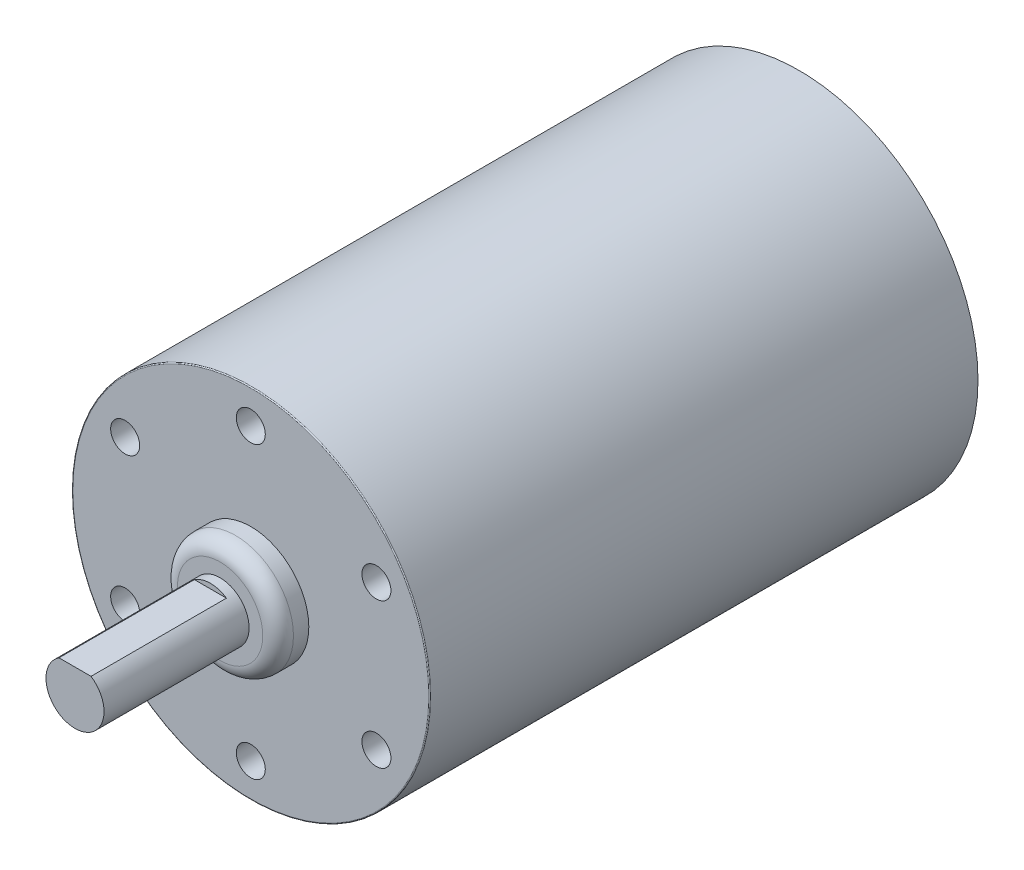
SolidWorks part; units mm, degrees
ref_plane "Front Plane" through (0, 0, 0) normal (0, 0, 1) x (1, 0, 0)
ref_plane "Top Plane" through (0, 0, 0) normal (0, 1, 0) x (1, 0, 0)
ref_plane "Right Plane" through (0, 0, 0) normal (1, 0, 0) x (0, 0, -1)
sketch "Sketch1" plane through (0, 0, 0) normal (0, 0, 1) x (1, 0, 0)
  circle A0 centre (0, 0) radius 18.5
  dimension "D1" = 37
extrude "Boss-Extrude1" add sketch "Sketch1" along normal blind 56.6928
fillet "Fillet3" radius 0.1 1 edges at (18.5, 0, 56.6928)
sketch "Sketch2" plane through (0, 0, 56.6928) normal (0, 0, 1) x (1, 0, 0)
  circle A0 centre (0, 0) radius 6
  dimension "D1" = 12
extrude "Boss-Extrude2" add sketch "Sketch2" along normal blind 3.175
fillet "Fillet2" radius 1.5875 1 edges at (6, 0, 59.8678)
sketch "Sketch5" plane through (0, 0, 59.8678) normal (0, 0, 1) x (1, 0, 0)
  circle A0 centre (0, 0) radius 3
  dimension "D1" = 6
extrude "Boss-Extrude3" add sketch "Sketch5" along normal blind 15
sketch "Sketch6" plane through (0, 0, 74.8678) normal (0, 0, 1) x (1, 0, 0)
  line L0 (-1.6583, 2.5) -> (1.6583, 2.5)
  circle A0 centre (0, 0) radius 3 construction
  circle A1 centre (0, 0) radius 3 construction
  arc A2 (-1.6583, 2.5) -> (1.6583, 2.5) centre (0, 0) cw
  point P7 (0, -3)
  point P8 (0, 0)
  point P9 (0, 0)
  point P10 (1.6583, 2.5)
  point P11 (0, 0)
  dimension "D1" = 5.5
extrude "Cut-Extrude1" cut sketch "Sketch6" against normal blind 14
sketch "Sketch7" plane through (0, 0, 56.6928) normal (0, 0, 1) x (1, 0, 0)
  circle A0 centre (0, 0) radius 15 construction
  circle A1 centre (0, 15) radius 1.5
  circle A2 centre (0, 0) radius 18.5 construction
  circle A3 centre (12.9904, 7.5) radius 1.5
  circle A4 centre (12.9904, -7.5) radius 1.5
  circle A5 centre (0, -15) radius 1.5
  circle A6 centre (-12.9904, -7.5) radius 1.5
  circle A7 centre (-12.9904, 7.5) radius 1.5
  point P6 (0, 16.5)
  point P8 (0, 18.5)
  point P9 (0, 0)
  point P10 (0, -15.2)
  point P22 (0, 0)
  dimension "D1" = 30
  dimension "D2" = 3
  dimension "D3" = 6
extrude "Cut-Extrude2" cut sketch "Sketch7" against normal blind 10
